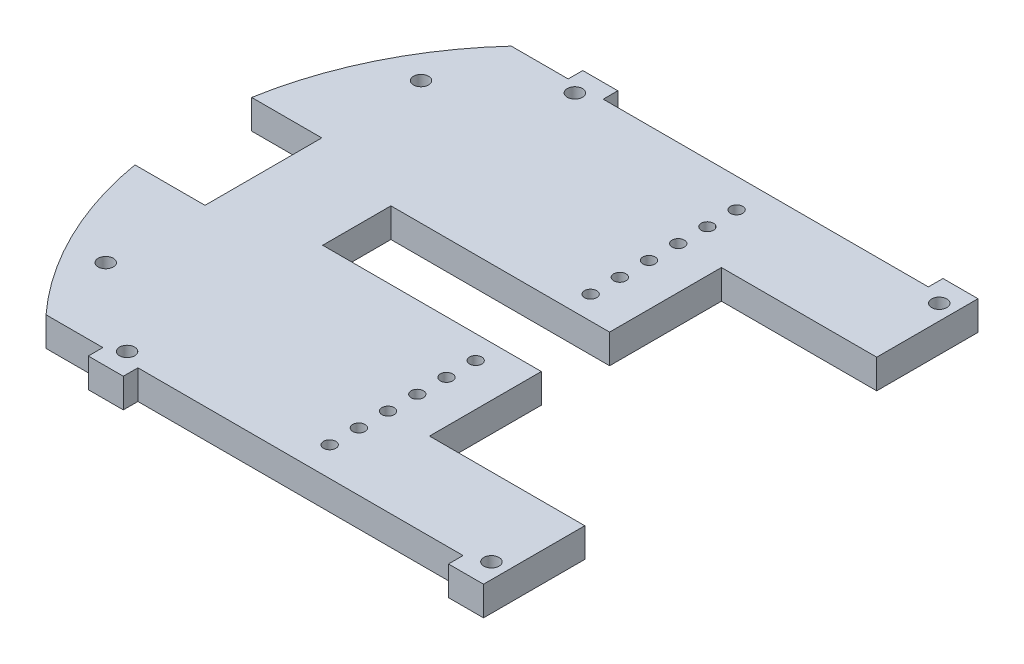
SolidWorks part; units mm, degrees
material "Acrylic (Medium-high impact)"
ref_plane "Front Plane" through (0, 0, 0) normal (0, 0, 1) x (1, 0, 0)
ref_plane "Top Plane" through (0, 0, 0) normal (0, 1, 0) x (1, 0, 0)
ref_plane "Right Plane" through (0, 0, 0) normal (1, 0, 0) x (0, 0, -1)
sketch "Sketch1" plane through (0, 0, 0) normal (0, 1, 0) x (1, 0, 0)
  line L0 (33.7767, 18.1873) -> (4.6272, 18.1873)
  line L1 (-30.9328, 38.3108) -> (-15.6928, 38.3108)
  line L2 (-15.6928, 38.3108) -> (-15.6928, 12.9108)
  line L3 (7.62, -24.9927) -> (78.3483, -24.9927)
  line L4 (33.7767, 18.1873) -> (52.1917, 18.1873)
  line L5 (52.1917, 18.1873) -> (52.1917, -6.1392)
  line L6 (52.1917, -6.1392) -> (85.9683, -6.1392)
  line L7 (85.9683, -6.1392) -> (85.9683, -24.9927)
  line L8 (42.9842, 0.9728) -> (42.9842, 18.1873) construction
  line L9 (82.6111, -23.0877) -> (82.6111, -6.1392) construction
  line L10 (82.6111, -23.0877) -> (85.9683, -23.0877) construction
  line L11 (3.3572, -23.0877) -> (3.3572, -6.1392) construction
  line L12 (3.3572, -23.0877) -> (0, -23.0877) construction
  line L13 (0, 76.2143) -> (0, 79.3893)
  line L14 (7.62, 76.2143) -> (7.62, 79.3893)
  line L15 (-30.9328, 25.6108) -> (90.9164, 25.6108) construction
  line L16 (-30.9328, 38.3108) -> (-30.9328, 12.9108) construction
  line L17 (90.9164, 24.0233) -> (90.9164, 27.1983) construction
  line L18 (3.3572, 74.3093) -> (0, 74.3093) construction
  line L19 (3.3572, 74.3093) -> (3.3572, 57.3608) construction
  line L20 (82.6111, 74.3093) -> (85.9683, 74.3093) construction
  line L21 (82.6111, 74.3093) -> (82.6111, 57.3608) construction
  line L22 (42.9842, 50.2488) -> (42.9842, 33.0343) construction
  line L23 (85.9683, 57.3608) -> (85.9683, 76.2143)
  line L24 (52.1917, 57.3608) -> (85.9683, 57.3608)
  line L25 (52.1917, 33.0343) -> (52.1917, 57.3608)
  line L26 (33.7767, 33.0343) -> (52.1917, 33.0343)
  line L27 (7.62, 76.2143) -> (78.3483, 76.2143)
  line L28 (-15.6928, 12.9108) -> (-30.9328, 12.9108)
  line L30 (33.7767, 33.0343) -> (4.6272, 33.0343)
  line L31 (78.3483, 76.2143) -> (78.3483, 79.3893)
  line L32 (0, 76.2143) -> (-12.3719, 76.2143)
  line L33 (4.6272, 33.0343) -> (4.6272, 18.1873)
  line L34 (0, -24.9927) -> (-12.3719, -24.9927)
  line L35 (78.3483, 79.3893) -> (85.9683, 79.3893)
  line L36 (85.9683, 76.2143) -> (85.9683, 79.3893)
  line L37 (7.62, 79.3893) -> (0, 79.3893)
  line L38 (78.3483, -24.9927) -> (78.3483, -28.1677)
  line L39 (85.9683, -24.9927) -> (85.9683, -28.1677)
  line L40 (78.3483, -28.1677) -> (85.9683, -28.1677)
  line L41 (7.62, -24.9927) -> (7.62, -28.1677)
  line L42 (0, -24.9927) -> (0, -28.1677)
  line L43 (7.62, -28.1677) -> (0, -28.1677)
  circle A0 centre (3.3572, -23.0877) radius 1.651
  circle A1 centre (82.6111, -23.0877) radius 1.651
  circle A2 centre (42.9842, -12.2927) radius 1.3335
  circle A3 centre (42.9842, -18.6427) radius 1.3335
  circle A4 centre (42.9842, -5.9427) radius 1.3335
  circle A5 centre (42.9842, 0.4073) radius 1.3335
  circle A6 centre (42.9842, 6.7573) radius 1.3335
  circle A7 centre (42.9842, 13.1073) radius 1.3335
  circle A8 centre (42.9842, 38.1143) radius 1.3335
  circle A9 centre (82.6111, 74.3093) radius 1.651
  circle A10 centre (3.3572, 74.3093) radius 1.651
  arc A11 (-30.9328, 12.9108) -> (110.2551, -7.5497) centre (42.9842, 25.6108) ccw construction
  arc A12 (-12.3719, 76.2143) -> (-30.9328, 38.3108) centre (42.9842, 25.6108) ccw
  arc A13 (110.2551, 58.7714) -> (-30.9328, 38.3108) centre (42.9842, 25.6108) ccw construction
  arc A14 (-12.3719, -24.9927) -> (-30.9328, 12.9108) centre (42.9842, 25.6108) cw
  circle A15 centre (-15.6928, 59.9008) radius 1.651
  circle A16 centre (-15.6928, -8.6792) radius 1.651
  circle A17 centre (-15.6928, 59.9008) radius 1.651 construction
  circle A18 centre (42.9842, 44.4643) radius 1.3335
  circle A19 centre (42.9842, 50.8143) radius 1.3335
  circle A20 centre (42.9842, 57.1643) radius 1.3335
  circle A21 centre (42.9842, 63.5143) radius 1.3335
  circle A22 centre (42.9842, 69.8643) radius 1.3335
  dimension "D8" = 2.667
  dimension "D1" = 33.7767
  dimension "D2" = 63.5
  dimension "D3" = 6.35
  dimension "D4" = 20.32
  dimension "D5" = 116.9011
  dimension "D6" = 3.175
  dimension "D7" = 7.62
  dimension "D9" = 43.18
  dimension "D10" = 6
extrude "Boss-Extrude1" add sketch "Sketch1" along normal blind 6.35
